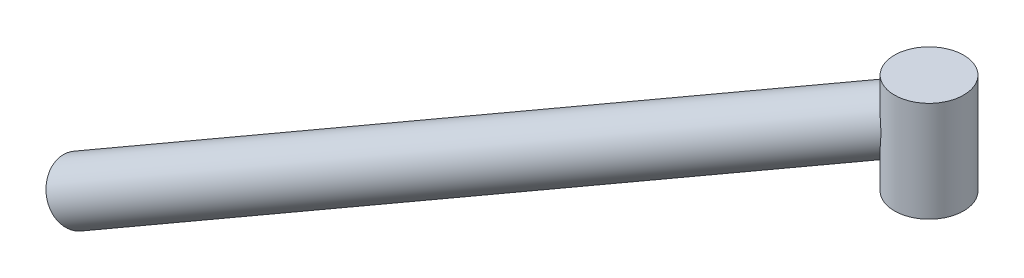
SolidWorks part; units mm, degrees
ref_plane "Front Plane" through (0, 0, 0) normal (0, 0, 1) x (1, 0, 0)
ref_plane "Top Plane" through (0, 0, 0) normal (0, 1, 0) x (1, 0, 0)
ref_plane "Right Plane" through (0, 0, 0) normal (1, 0, 0) x (0, 0, -1)
sketch "Base Sketch" plane through (0, 0, 0) normal (0, 1, 0) x (1, 0, 0)
  circle A0 centre (-6.4, 79) radius 5
extrude "Base" add sketch "Base Sketch" along normal blind 14.5 from offset 36.5
ref_axis "Engine Axis" through (5.1013, 0, 0) along (-1, 0, 0)
ref_plane "Whip Plane" through (0, 0, -79) normal (0, 0, 1) x (1, 0, 0)
sketch "Whip Sketch" plane through (0, 0, -79) normal (0, 0, 1) x (1, 0, 0)
  line L0 (-2.0699, 48.5) -> (-133.7057, -27.5) construction
  line L1 (-6.4, 46) -> (-129.3756, -25)
  line L2 (-129.3756, -25) -> (-127.3256, -28.5507)
  line L3 (-127.3256, -28.5507) -> (-4.35, 42.4493)
  line L4 (-4.35, 42.4493) -> (-6.4, 46)
revolve "Whip" add sketch "Whip Sketch" angle 360 about L0
